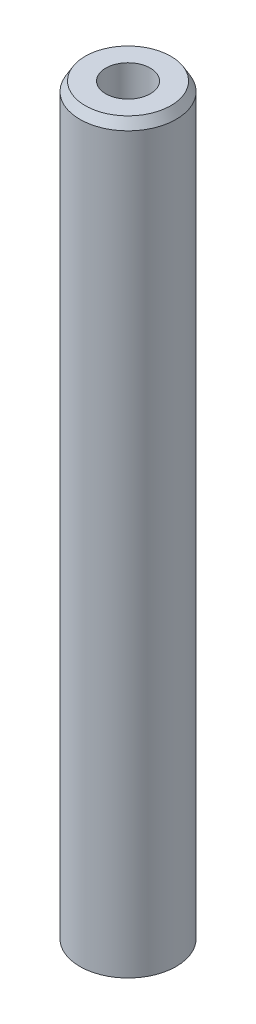
SolidWorks part; units mm, degrees
ref_plane "Front Plane" through (0, 0, 0) normal (0, 0, 1) x (1, 0, 0)
ref_plane "Top Plane" through (0, 0, 0) normal (0, 1, 0) x (1, 0, 0)
ref_plane "Right Plane" through (0, 0, 0) normal (1, 0, 0) x (0, 0, -1)
sketch "Sketch1" plane through (0, 0, 0) normal (0, 1, 0) x (1, 0, 0)
  circle A0 centre (0, 0) radius 15
  dimension "SHAFT_OD" = 30
extrude "Boss-Extrude1" add sketch "Sketch1" along normal blind 233.1224
sketch "Sketch2" plane through (0, 0, 0) normal (0, 1, 0) x (1, 0, 0)
  circle A0 centre (0, 0) radius 6.9467
  dimension "BORE_D" = 13.8934
extrude "Cut-Extrude1" cut sketch "Sketch2" along normal through all
chamfer "Chamfer1" distance 2.8709 angle 30 2 edges at (0, 233.1224, 15) (0, 0, 15) first distance on face at (0, 233.1224, 15) first distance on face at (0, 0, 6.9467)
